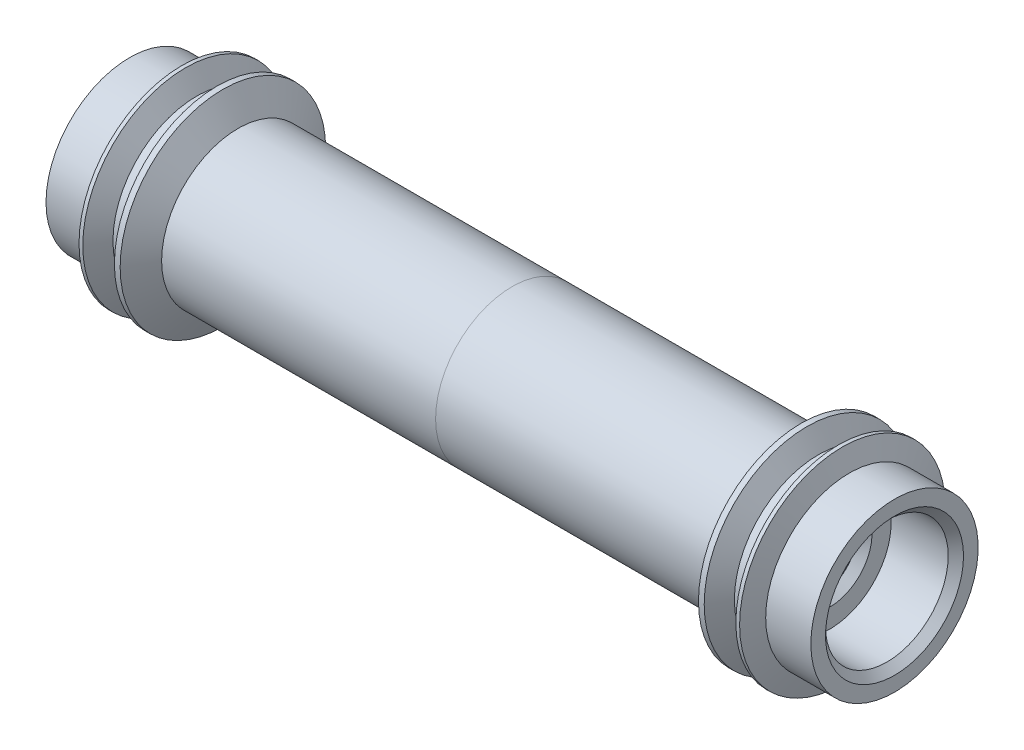
SolidWorks part; units mm, degrees
ref_plane "Front Plane" through (0, 0, 0) normal (0, 0, 1) x (1, 0, 0)
ref_plane "Top Plane" through (0, 0, 0) normal (0, 1, 0) x (1, 0, 0)
ref_plane "Right Plane" through (0, 0, 0) normal (1, 0, 0) x (0, 0, -1)
sketch "Sketch2" plane through (0, 0, 0) normal (0, 0, 1) x (1, 0, 0)
  line L0 (0, 0) -> (0, 28.4375) construction
  line L1 (-25.4, 4.075) -> (-21.1, 4.075) construction
  line L2 (-25.4, 4.075) -> (-25.4, -4.075) construction
  line L3 (-25.4, -4.075) -> (-21.1, -4.075) construction
  line L4 (-21.1, 4.075) -> (-21.1, -4.075) construction
  line L5 (-25.4, 4.075) -> (-21.1, -4.075) construction
  line L6 (-25.4, -4.075) -> (-21.1, 4.075) construction
  line L7 (21.1, 4.5) -> (42.4832, 4.5) construction
  line L8 (21.1, 4.5) -> (21.1, -4.5) construction
  line L9 (21.1, -4.5) -> (42.4832, -4.5) construction
  line L10 (42.4832, 4.5) -> (42.4832, -4.5) construction
  line L11 (21.1, 4.5) -> (42.4832, -4.5) construction
  line L12 (21.1, -4.5) -> (42.4832, 4.5) construction
  line L13 (-25.4, 0) -> (42.4832, 0) construction
  line L14 (-25.4, 5.5562) -> (-22.4, 5.5562)
  line L15 (-22.4, 5.5562) -> (-21.9378, 6.8262)
  line L16 (-21.9378, 6.8262) -> (-21.6882, 6.8262)
  line L19 (-19.5868, 6.8262) -> (-19.2058, 6.8262)
  line L20 (-19.2058, 6.8262) -> (-18.1976, 5.08)
  line L21 (-18.1976, 5.08) -> (0, 5.08)
  line L22 (-25.4, 5.5562) -> (-25.4, 4.075)
  line L23 (-25.4, 4.075) -> (-21.1, 4.075)
  line L24 (-21.1, 4.075) -> (-21.1, 0)
  line L25 (-21.1, 0) -> (0, 0)
  line L26 (0, 0) -> (0, 5.08)
  line L27 (-33.5594, -5.5562) -> (-33.5594, 5.5562) construction
  line L28 (-20.6375, 5.5562) -> (-20.6375, 7.68) construction
  line L29 (-20.6375, 5.5562) -> (20.6375, 5.5562) construction
  line L30 (-25.4, 5.5562) -> (25.4, 5.5562) construction
  line L31 (0, 1.625) -> (-12.5, 1.625)
  line L32 (-12.5, 1.625) -> (-14.125, 0)
  line L33 (-12.5, 1.625) -> (-12.5, -1.625) construction
  line L34 (-12.5, 1.625) -> (12.5, 1.625) construction
  line L35 (-21.1, 1.905) -> (-15.448, 1.905)
  line L36 (-15.448, 1.905) -> (-15.448, 0)
  line L37 (-21.1, 2.805) -> (-20.592, 2.297)
  line L38 (-15.448, 1.905) -> (-28.448, 1.905) construction
  line L39 (-15.448, 1.905) -> (-15.448, -1.905) construction
  line L40 (-15.448, -1.905) -> (-28.448, -1.905) construction
  line L41 (-28.448, 1.905) -> (-28.448, -1.905) construction
  line L42 (-20.592, 2.297) -> (-20.592, 0)
  line L43 (-20.955, 5.5562) -> (-20.32, 5.5562)
  line L44 (-20.32, 5.5562) -> (-19.5868, 6.8262)
  line L45 (-21.6882, 6.8262) -> (-20.955, 5.5562)
  point P0 (-23.25, 0)
  point P5 (31.7916, 0)
  point P27 (-33.5594, 0)
  point P28 (-19.3963, 6.8262)
  point P29 (-12.5, 0)
  point P33 (0, 5.5562)
  point P36 (0, 1.625)
  point P48 (-15.448, 0)
  point P51 (0, 5.5562)
  point P54 (-20.6375, 5.5562)
  dimension "D1" = 4.3
  dimension "D3" = 5.08
  dimension "D4" = 11.1125
  dimension "D5" = 8.15
  dimension "D6" = 60
  dimension "D8" = 1.27
  dimension "D9" = 70
  dimension "D10" = 41.275
  dimension "D12" = 0.381
  dimension "D13" = 45
  dimension "D14" = 25
  dimension "D15" = 3.25
  dimension "D16" = 3.81
  dimension "D17" = 3.048
  dimension "D18" = 1.27
  dimension "D19" = 0.508
  dimension "D20" = 45
  dimension "D21" = 13
  dimension "D11" = 50.8
  dimension "D22" = 3
  dimension "D7" = 60
  dimension "D23" = 0.635
revolve "Revolve1" add sketch "Sketch2" angle 360 about L13 region at (-11.9088, 3.5065, 0)
chamfer "Chamfer1" distance 0.508 angle 45 1 edges at (-25.4, 0, 4.075)
mirror "Mirror1" about plane through (0, 0, 0) normal (1, 0, 0) of bodies 101
equation "\"D15@Sketch2\"=3mm+.25mm"
equation "\"D1@Sketch2\"=4.3mm"
